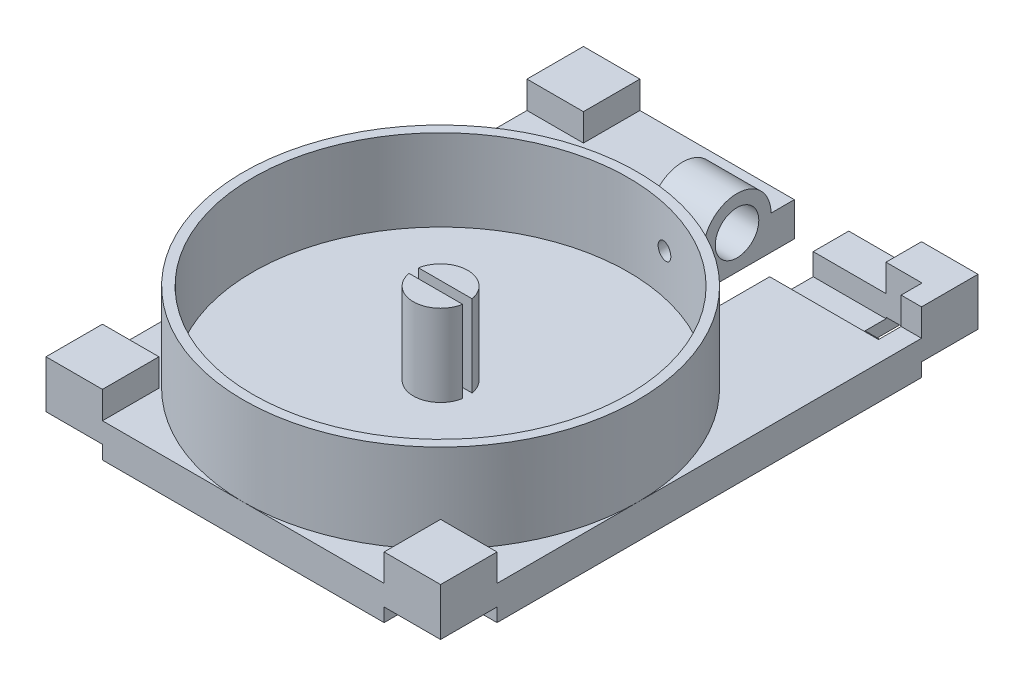
SolidWorks part; units mm, degrees
ref_plane "Front Plane" through (0, 0, 0) normal (0, 0, 1) x (1, 0, 0)
ref_plane "Top Plane" through (0, 0, 0) normal (0, 1, 0) x (1, 0, 0)
ref_plane "Right Plane" through (0, 0, 0) normal (1, 0, 0) x (0, 0, -1)
sketch "Sketch1" plane through (0, 0, 0) normal (0, 1, 0) x (1, 0, 0)
  line L1 (-113.2029, -5.5364) -> (-84.2029, -5.5364)
  line L2 (-113.2029, -5.5364) -> (-113.2029, -55.5364)
  line L3 (-113.2029, -55.5364) -> (-84.2029, -55.5364)
  line L4 (-84.2029, -5.5364) -> (-84.2029, -55.5364)
extrude "Boss-Extrude1" add sketch "Sketch1" along normal blind 2.5
sketch "Sketch2" plane through (0, 2.5, 0) normal (0, 1, 0) x (1, 0, 0)
  line L0 (-98.7029, -55.5364) -> (-98.7029, -41.0364)
  line L1 (-113.2029, -55.5364) -> (-84.2029, -55.5364) construction
  circle A0 centre (-98.7029, -41.0364) radius 13.8
  circle A1 centre (-98.7029, -41.0364) radius 14.5
extrude "Boss-Extrude3" add sketch "Sketch2" along normal blind 6 contours A1 A0 region at (-108.6659, 2.5, 31.0733)
sketch "Sketch3" plane through (0, 2.5, 0) normal (0, 1, 0) x (1, 0, 0)
  line L0 (-98.7029, -41.0364) -> (-98.7029, -40.6864)
  line L1 (-98.7029, -40.6864) -> (-102.3011, -40.6864)
  line L3 (-102.3011, -40.6864) -> (-94.9312, -40.6864)
  line L4 (-102.3011, -40.6864) -> (-102.3011, -41.3864)
  line L5 (-102.3011, -41.3864) -> (-94.9312, -41.3864)
  line L6 (-94.9312, -40.6864) -> (-94.9312, -41.3864)
  circle A0 centre (-98.7029, -41.0364) radius 2
extrude "Boss-Extrude4" add sketch "Sketch3" along normal blind 6 contours L3 A0 L1 | L5 A0 region at (-98.7029, 2.5, 39.9955) region at (-98.7029, 2.5, 42.0772)
sketch "Sketch4" plane through (0, 2.5, 0) normal (0, 1, 0) x (1, 0, 0)
  line L0 (-98.7029, -26.5364) -> (-98.7029, -20.2485)
  line L2 (-98.7029, -20.2485) -> (-97.7029, -20.2485)
  line L3 (-97.7029, -20.2485) -> (-97.7029, -14.2485)
  line L4 (-97.7029, -20.2485) -> (-97.7029, -26.2485)
  line L5 (-97.7029, -26.2485) -> (-93.7029, -26.2485)
  line L6 (-93.7029, -26.2485) -> (-93.7029, -14.2485)
  line L7 (-93.7029, -14.2485) -> (-97.7029, -14.2485)
  arc A1 (-84.2029, -41.0364) -> (-113.2029, -41.0364) centre (-98.7029, -41.0364) ccw construction
extrude "Cut-Extrude1" cut sketch "Sketch4" against normal blind 6 contours L6 L7 L3 L4 L5 region at (-95.7029, 2.5, 20.2485)
sketch "Sketch5" plane through (0, 0, 26.2485) normal (0, 0, -1) x (-1, 0, 0)
  line L0 (95.7029, 2.5) -> (95.7029, 6)
  line L1 (97.7029, 2.5) -> (93.7029, 2.5) construction
  circle A0 centre (95.7029, 6) radius 0.6
extrude "Cut-Extrude2" cut sketch "Sketch5" against normal blind 6 contours A0 region at (-96.1151, 5.5877, 26.2485)
sketch "Sketch6" plane through (-97.7029, 0, 0) normal (1, 0, 0) x (0, 0, -1)
  line L0 (-26.2485, 2.5) -> (-14.2485, 2.5) construction
  circle A0 centre (-20.2485, 2.5) radius 1.6
extrude "Cut-Extrude3" cut sketch "Sketch6" against normal blind 4 and the other way blind 10
sketch "Sketch7" plane through (-97.7029, 0, 0) normal (1, 0, 0) x (0, 0, -1)
  line L0 (-21.8485, 2.5) -> (-18.6485, 2.5)
  line L1 (-18.6485, 2.5) -> (-14.2485, 2.5) construction
  arc A0 (-21.8485, 2.5) -> (-18.6485, 2.5) centre (-20.2485, 2.5) ccw construction
  circle A1 centre (-20.2485, 2.5) radius 1.6
  circle A2 centre (-20.2485, 2.5) radius 2.5
  line M3 (-14.2485, 2.5) -> (-18.6485, 2.5)
  arc M4 (-18.6485, 2.5) -> (-21.8485, 2.5) centre (-20.2485, 2.5) cw
  line M5 (-21.8485, 2.5) -> (-26.2485, 2.5)
extrude "Boss-Extrude6" add sketch "Sketch7" against normal blind 4 contours A2 A1 M3 M5 | A2 M5 M3 M4 region at (-97.7029, 2.5559, 22.2985) region at (-97.7029, 0.8441, 20.2485)
sketch "Sketch8" plane through (-93.7029, 0, 0) normal (-1, 0, 0) x (0, 0, 1)
  line L0 (18.6485, 2.5) -> (21.8485, 2.5)
  line L5 (20.2485, 2.5) -> (20.2485, 0.9)
  line L6 (20.2485, 0.9) -> (18.6485, 0.9)
  line L7 (18.6485, 0.9) -> (18.6485, 2.5)
  line L9 (20.2485, 0.9) -> (21.8485, 0.9)
  line L10 (21.8485, 0.9) -> (21.8485, 2.5)
  arc A0 (18.6485, 2.5) -> (21.8485, 2.5) centre (20.2485, 2.5) ccw construction
  arc M11 (21.8485, 2.5) -> (18.6485, 2.5) centre (20.2485, 2.5) cw
extrude "Cut-Extrude4" cut sketch "Sketch8" against normal blind 8 contours L0 L5 M11 | L5 L0 M11 | L7 L6 M11 | L9 L10 M11 region at (-93.7029, 1.2574, 19.0059) region at (-93.7029, 1.8209, 19.5695) region at (-93.7029, 1.8209, 20.9276) region at (-93.7029, 1.2574, 21.4911)
sketch "Sketch9" plane through (0, 2.5, 0) normal (0, 1, 0) x (1, 0, 0)
  line L0 (-113.2029, -55.5364) -> (-113.2029, -16.0364)
  line L1 (-113.2029, -5.5364) -> (-113.2029, -41.0364) construction
  line L2 (-113.2029, -16.0364) -> (-84.2029, -16.0364)
  line L3 (-84.2029, -41.0364) -> (-84.2029, -5.5364) construction
  line L4 (-84.2029, -16.0364) -> (-84.2029, -5.5364)
  line L5 (-84.2029, -5.5364) -> (-113.2029, -5.5364)
  line L6 (-113.2029, -5.5364) -> (-113.2029, -16.0364)
  line M12 (-97.7029, -17.7485) -> (-97.7029, -14.2485)
  line M13 (-97.7029, -14.2485) -> (-93.7029, -14.2485)
  line M14 (-93.7029, -14.2485) -> (-93.7029, -18.6485)
  line M17 (-84.2029, -41.0364) -> (-84.2029, -5.5364)
  line M18 (-84.2029, -5.5364) -> (-113.2029, -5.5364)
  line M19 (-113.2029, -5.5364) -> (-113.2029, -41.0364)
extrude "Cut-Extrude5" cut sketch "Sketch9" against normal blind 5 contours L2 M19 M12 M13 M14 M17 M18 region at (-98.775, 2.5, 10.6816)
sketch "Sketch10" plane through (0, 0, 0) normal (0, -1, 0) x (1, 0, 0)
  line L0 (-98.7029, 55.5364) -> (-98.7029, 41.0364)
  line L1 (-113.2029, 55.5364) -> (-84.2029, 55.5364) construction
  line L3 (-113.2029, 16.0364) -> (-109.0529, 16.0364)
  line L4 (-113.2029, 16.0364) -> (-113.2029, 20.1864)
  line L5 (-113.2029, 20.1864) -> (-109.0529, 20.1864)
  line L6 (-109.0529, 16.0364) -> (-109.0529, 20.1864)
  line L7 (-84.2029, 16.0364) -> (-88.3529, 16.0364)
  line L8 (-84.2029, 16.0364) -> (-84.2029, 20.1864)
  line L9 (-84.2029, 20.1864) -> (-88.3529, 20.1864)
  line L10 (-88.3529, 16.0364) -> (-88.3529, 20.1864)
  line L11 (-113.2029, 55.5364) -> (-109.0529, 55.5364)
  line L12 (-113.2029, 55.5364) -> (-113.2029, 51.3864)
  line L13 (-113.2029, 51.3864) -> (-109.0529, 51.3864)
  line L14 (-109.0529, 55.5364) -> (-109.0529, 51.3864)
  line L15 (-84.2029, 55.5364) -> (-88.3529, 55.5364)
  line L16 (-84.2029, 55.5364) -> (-84.2029, 51.3864)
  line L17 (-84.2029, 51.3864) -> (-88.3529, 51.3864)
  line L18 (-88.3529, 55.5364) -> (-88.3529, 51.3864)
  circle A0 centre (-98.7029, 41.0364) radius 12.5
  line M4 (-93.7029, 16.0364) -> (-84.2029, 16.0364)
  line M5 (-84.2029, 16.0364) -> (-84.2029, 55.5364)
  line M6 (-84.2029, 55.5364) -> (-113.2029, 55.5364)
  line M7 (-113.2029, 55.5364) -> (-113.2029, 16.0364)
  line M8 (-113.2029, 16.0364) -> (-97.7029, 16.0364)
extrude "Cut-Extrude7" cut sketch "Sketch10" against normal blind 1 contours L14 L13 M6 M7 | L18 L17 M6 M5 | A0 | L6 L5 M8 M7 | L10 L9 M4 M5 region at (-90.114, 0, 49.6252) region at (-86.2779, 0, 18.1114) region at (-86.2779, 0, 53.4614) region at (-111.1279, 0, 18.1114) region at (-111.1279, 0, 53.4614)
sketch "Sketch11" plane through (0, 2.5, 0) normal (0, 1, 0) x (1, 0, 0)
  line L0 (-88.3529, -18.6485) -> (-85.7029, -18.6485)
  line L1 (-113.2029, -55.5364) -> (-109.0529, -55.5364)
  line L2 (-113.2029, -55.5364) -> (-113.2029, -51.3864)
  line L3 (-113.2029, -51.3864) -> (-109.0529, -51.3864)
  line L4 (-109.0529, -55.5364) -> (-109.0529, -51.3864)
  line L5 (-84.2029, -55.5364) -> (-88.3529, -55.5364)
  line L6 (-84.2029, -55.5364) -> (-84.2029, -51.3864)
  line L7 (-84.2029, -51.3864) -> (-88.3529, -51.3864)
  line L8 (-88.3529, -55.5364) -> (-88.3529, -51.3864)
  line L9 (-113.2029, -16.0364) -> (-109.0529, -16.0364)
  line L10 (-113.2029, -16.0364) -> (-113.2029, -20.1864)
  line L11 (-113.2029, -20.1864) -> (-109.0529, -20.1864)
  line L12 (-109.0529, -16.0364) -> (-109.0529, -20.1864)
  line L13 (-84.2029, -16.0364) -> (-88.3529, -16.0364)
  line L14 (-84.2029, -16.0364) -> (-84.2029, -20.1864)
  line L15 (-84.2029, -20.1864) -> (-88.3529, -20.1864)
  line L16 (-88.3529, -16.0364) -> (-88.3529, -20.1864)
  line L17 (-85.7029, -18.6485) -> (-85.7029, -20.2485)
  line L18 (-85.7029, -18.6485) -> (-85.7029, -21.8485) construction
  line M18 (-113.2029, -41.0364) -> (-113.2029, -55.5364)
  line M19 (-113.2029, -55.5364) -> (-98.7029, -55.5364)
extrude "Boss-Extrude7" add sketch "Sketch11" along normal blind 2 contours L4 L3 M19 M18 | L8 L5 L6 L7 | L12 L9 L10 L11 | L0 L17 L15 L14 L13 L16 region at (-86.0454, 2.5, 17.7065) region at (-111.1279, 2.5, 53.4614) region at (-86.2779, 2.5, 53.4614) region at (-111.1279, 2.5, 18.1114)
sketch "Sketch13" plane through (0, 1, 0) normal (0, -1, 0) x (1, 0, 0)
  circle A0 centre (-111.1279, 53.4614) radius 1.1
  circle A1 centre (-86.2779, 53.4614) radius 1.1
  circle A2 centre (-111.1279, 18.1114) radius 1.1
  circle A3 centre (-86.2779, 18.1114) radius 1.1
extrude "Cut-Extrude8" cut sketch "Sketch13" against normal blind 1.1
sketch "Sketch14" plane through (0, 1, 0) normal (0, -1, 0) x (1, 0, 0)
  circle A0 centre (-98.7029, 41.0364) radius 12.5
extrude "Cut-Extrude9" cut sketch "Sketch14" against normal blind 1
sketch "Sketch15" plane through (0, 2.5, 0) normal (0, 1, 0) x (1, 0, 0)
  circle A0 centre (-98.7029, -41.0364) radius 13.8
extrude "Boss-Extrude8" add sketch "Sketch15" along normal blind 0.5
sketch "Sketch16" plane through (0, 8.5, 0) normal (0, 1, 0) x (1, 0, 0)
  line L0 (-96.7337, -41.3864) -> (-100.672, -41.3864)
  line L2 (-100.672, -40.6864) -> (-96.7337, -40.6864)
  circle A0 centre (-98.7029, -41.0364) radius 2
  circle A1 centre (-98.7029, -41.0364) radius 13.8
  circle A2 centre (-98.7029, -41.0364) radius 14.5
  line M3 (-100.672, -40.6864) -> (-96.7337, -40.6864)
  arc M4 (-96.7337, -40.6864) -> (-100.672, -40.6864) centre (-98.7029, -41.0364) ccw
extrude "Boss-Extrude9" add sketch "Sketch16" along normal blind 0.5 contours A2 A1 | M4 M3 | L0 A0 region at (-98.7029, 8.5, 42.0772) region at (-98.7029, 8.5, 39.9955) region at (-112.7928, 8.5, 41.0364)
